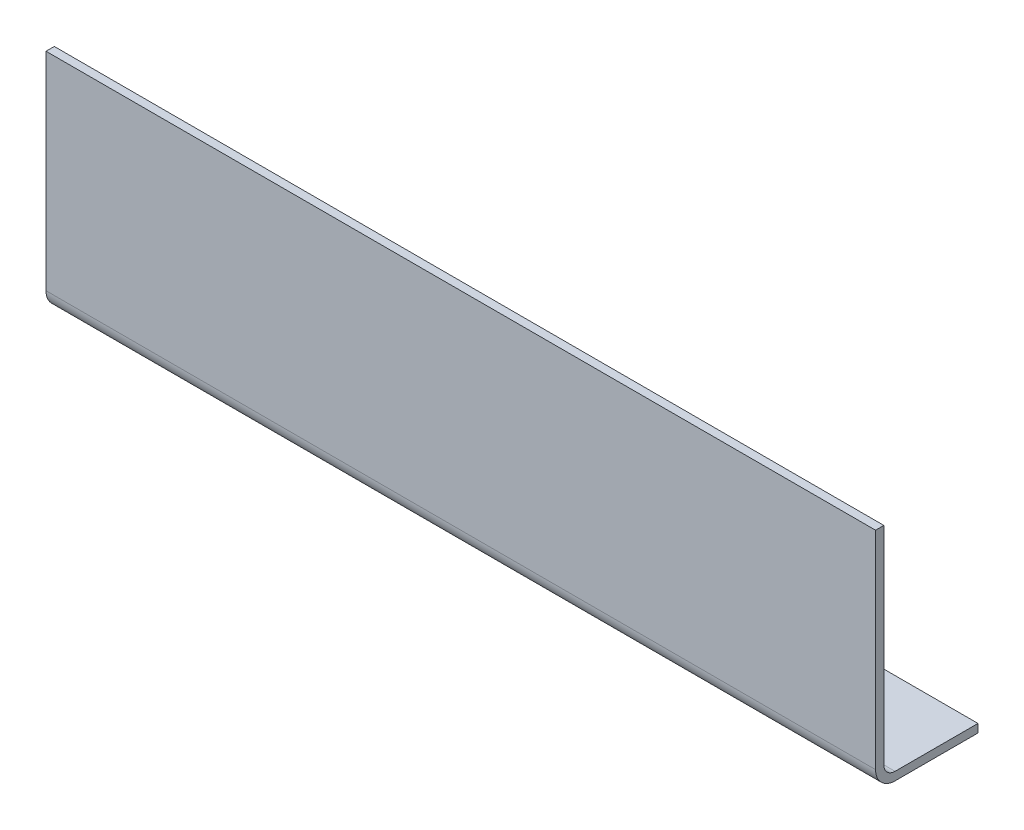
SolidWorks part; units mm, degrees
ref_plane "Front Plane" through (0, 0, 0) normal (0, 0, 1) x (1, 0, 0)
ref_plane "Top Plane" through (0, 0, 0) normal (0, 1, 0) x (1, 0, 0)
ref_plane "Right Plane" through (0, 0, 0) normal (1, 0, 0) x (0, 0, -1)
sketch "Sketch1" plane through (0, 0, 0) normal (1, 0, 0) x (0, 0, -1)
  line L0 (0, 41.9244) -> (0, -41.9244) construction
  line L1 (-4, 3.7465) -> (-4, -46.2535)
  line L2 (0.7, -50.9535) -> (20.7, -50.9535)
  line L3 (20.7, -50.9535) -> (20.7, -48.9535)
  line L4 (20.7, -48.9535) -> (0.7, -48.9535)
  line L5 (-2, -46.2535) -> (-2, 3.7465)
  line L6 (-2, 3.7465) -> (-4, 3.7465)
  arc A0 (-4, -46.2535) -> (0.7, -50.9535) centre (0.7, -46.2535) ccw
  arc A1 (0.7, -48.9535) -> (-2, -46.2535) centre (0.7, -46.2535) cw
  dimension "D3" = 2.7
  dimension "D4" = 4.7
  dimension "D1" = 4
  dimension "D2" = 8
  dimension "D5" = 2
  dimension "D6" = 50
  dimension "D7" = 20
extrude "Boss-Extrude1" add sketch "Sketch1" along normal mid plane 200
